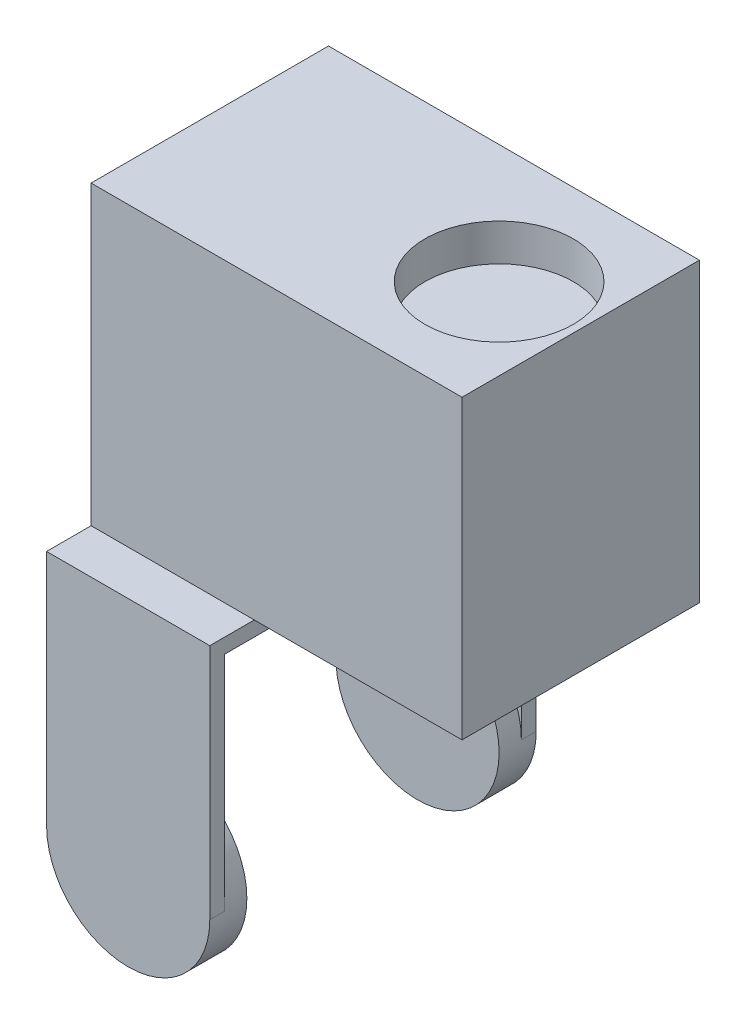
SolidWorks part; units mm, degrees
ref_plane "Front Plane" through (0, 0, 0) normal (0, 0, 1) x (1, 0, 0)
ref_plane "Top Plane" through (0, 0, 0) normal (0, 1, 0) x (1, 0, 0)
ref_plane "Right Plane" through (0, 0, 0) normal (1, 0, 0) x (0, 0, -1)
sketch "Sketch1" plane through (0, 0, 0) normal (0, 0, 1) x (1, 0, 0)
  line L1 (-25, 20) -> (25, 20)
  line L2 (-25, 20) -> (-25, -20)
  line L3 (-25, -20) -> (25, -20)
  line L4 (25, 20) -> (25, -20)
  line L5 (-25, 20) -> (25, -20) construction
  line L6 (-25, -20) -> (25, 20) construction
  line L7 (-25, -20) -> (-3, -20)
  line L8 (-25, -20) -> (-25, -52)
  line L9 (-25, -52) -> (-3, -52)
  line L10 (-3, -20) -> (-3, -52)
  circle A0 centre (-14, -52) radius 11
  point P0 (0, 0)
  dimension "D1" = 50
  dimension "D2" = 40
  dimension "D3" = 22
  dimension "D4" = 32
extrude "Boss-Extrude1" add sketch "Sketch1" against normal blind 32 contours L4 L1 L2 L3 region at (0, 0, 0)
extrude "Boss-Extrude2" add sketch "Sketch1<3>" against normal blind 38 contours A0 L10 L3 L8 | L9 A0 | L9 A0 region at (-14, -31.8093, 0) region at (-14, -47.3315, 0) region at (-14, -56.6685, 0)
sketch "Sketch1<3>" plane through (0, 0, 0) normal (0, 0, 1) x (1, 0, 0) same geometry as "Sketch1"
extrude "Boss-Extrude3" add sketch "Sketch1<4>" along normal blind 6 contours A0 L10 L3 L8 | L9 A0 | L9 A0 region at (-14, -31.8093, 0) region at (-14, -47.3315, 0) region at (-14, -56.6685, 0)
sketch "Sketch1<4>" plane through (0, 0, 0) normal (0, 0, 1) x (1, 0, 0) same geometry as "Sketch1"
sketch "Sketch2" plane through (-25, 0, 0) normal (-1, 0, 0) x (0, 0, 1)
  line L0 (-32, -20) -> (0, -20)
  line L1 (-36, -63) -> (4, -63)
  line L4 (-36, -22) -> (4, -22)
  line L5 (-36, -22) -> (-36, -63)
  line L7 (4, -22) -> (4, -63)
  line M10 (-38, -52) -> (6, -52)
  dimension "D1" = 41
  dimension "D2" = 41
extrude "Cut-Extrude1" cut sketch "Sketch2" against normal blind 22 contours L7 L4 L5 M10 | L7 L5 L1 M10 region at (-25, -57.5, -16) region at (-25, -37, -16)
sketch "Sketch3" plane through (0, 0, 4) normal (0, 0, -1) x (-1, 0, 0)
  line L0 (25, -52) -> (3, -52)
  circle A0 centre (14, -52) radius 11
  arc M4 (3, -52) -> (25, -52) centre (14, -52) ccw
extrude "Boss-Extrude5" add sketch "Sketch3" along normal blind 3 contours L0 A0 | L0 M4 region at (-14, -56.6685, 4) region at (-14, -47.3315, 4)
sketch "Sketch4" plane through (0, 0, -36) normal (0, 0, 1) x (1, 0, 0)
  line L0 (-25, -52) -> (-3, -52)
  circle A0 centre (-14, -52) radius 11
  arc M2 (-25, -52) -> (-3, -52) centre (-14, -52) ccw
extrude "Boss-Extrude6" add sketch "Sketch4" along normal blind 3 contours L0 A0 | L0 M2 region at (-14, -47.3315, -36) region at (-14, -56.6685, -36)
ref_plane "Plane8" through (0, -52, 0) normal (0, -1, 0) x (-1, 0, 0)
sketch "Sketch9" plane through (0, 0, -33) normal (0, 0, 1) x (1, 0, 0)
  point P0 (-14, -52)
sketch "Sketch10" plane through (0, 0, 1) normal (0, 0, -1) x (-1, 0, 0)
  point P0 (14, -52)
sketch "Sketch11" plane through (0, -52, 0) normal (0, -1, 0) x (-1, 0, 0)
  line L0 (14, 33) -> (14, -1)
  point P4 (14, 16)
ref_point "Point2"
ref_point "Point3"
sketch "Sketch13" plane through (0, 20, 0) normal (0, 1, 0) x (1, 0, 0)
  line L0 (0, 16) -> (25, 16)
  line L1 (25, 32) -> (25, 0) construction
  circle A0 centre (14, 16) radius 10
  point P5 (14, 16)
  dimension "D1" = 11
extrude "Cut-Extrude2" cut sketch "Sketch13" against normal blind 5 contours L0 A0 | L0 A0 region at (14, 20, -20.2441) region at (14, 20, -11.7559)
ref_point "Point4"
